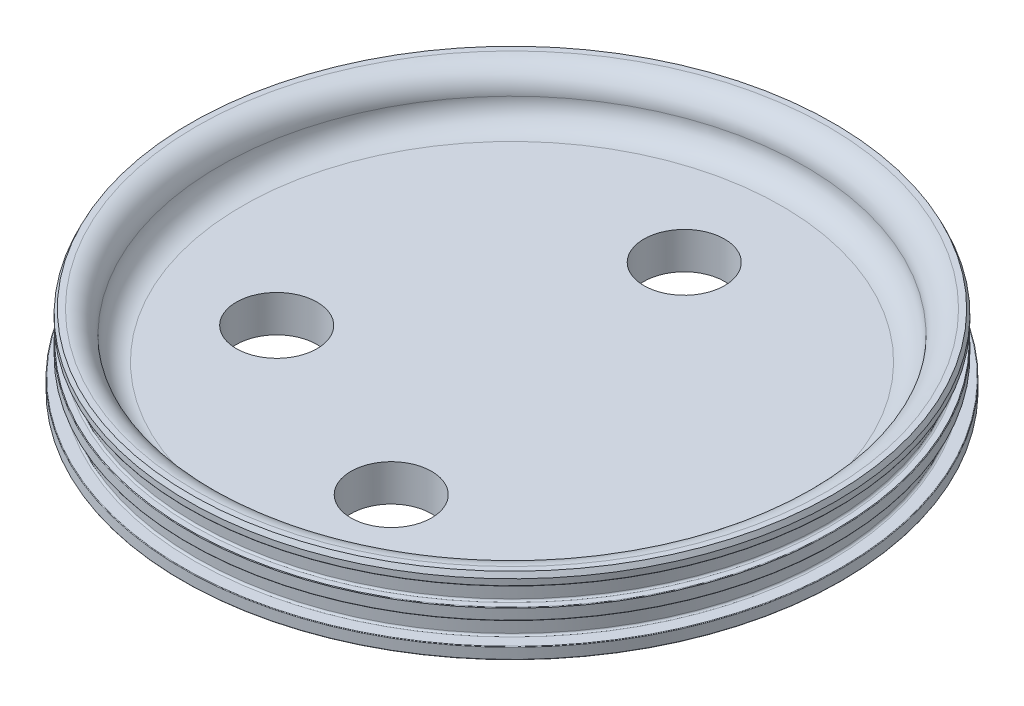
SolidWorks part; units mm, degrees
material "6061-T6 (SS)"
ref_plane "Front Plane" through (0, 0, 0) normal (0, 0, 1) x (1, 0, 0)
ref_plane "Top Plane" through (0, 0, 0) normal (0, 1, 0) x (1, 0, 0)
ref_plane "Right Plane" through (0, 0, 0) normal (1, 0, 0) x (0, 0, -1)
sketch "Sketch1" plane through (0, 0, 0) normal (0, 0, 1) x (1, 0, 0)
  line L0 (0, 48.1922) -> (0, -25.6743) construction
  line L1 (0, 0) -> (72.898, 0)
  line L2 (72.898, 0) -> (72.898, 2.54)
  line L3 (72.898, 2.54) -> (69.8475, 2.54)
  line L4 (69.8475, 2.54) -> (69.8475, 6.604)
  line L5 (69.8475, 6.604) -> (71.6255, 6.604)
  line L6 (71.6255, 6.604) -> (71.6255, 9.144)
  line L7 (71.6255, 9.144) -> (69.8475, 9.144)
  line L8 (64.7675, 15.748) -> (64.7675, 5.588)
  line L9 (64.7675, 5.588) -> (0, 5.588)
  line L10 (0, 5.588) -> (0, 0)
  line L11 (69.8475, 9.144) -> (69.8475, 13.208)
  line L12 (69.8475, 13.208) -> (71.6255, 13.208)
  line L13 (71.6255, 13.208) -> (71.6255, 15.748)
  line L14 (71.6255, 15.748) -> (64.7675, 15.748)
  dimension "D2" = 4.064
  dimension "D5" = 5.588
  dimension "D7" = 4.064
  dimension "D3" = 2.54
  dimension "D4" = 2.54
  dimension "D8" = 5.08
  dimension "D9" = 10.16
  dimension "D1" = 72.898
  dimension "D6" = 3.0505
  dimension "D10" = 1.778
revolve "Revolve1" add sketch "Sketch1" angle 360 about L0
sketch "Sketch6" plane through (0, 0, 0) normal (0, -1, 0) x (1, 0, 0)
  circle A0 centre (0, 0) radius 66.04
  dimension "D1" = 132.08
extrude "Boss-Extrude1" add sketch "Sketch6" along normal blind 2.54
fillet "CNC ID Fillet" radius 0.4064 5 edges at (-69.8475, 6.604, 0) (-69.8475, 2.54, 0) (66.04, 0, 0) (-69.8475, 13.208, 0) (-69.8475, 9.144, 0)
fillet "CNC OD Fillet" radius 0.127 6 edges at (-71.6255, 6.604, 0) (-72.898, 2.54, 0) (-71.6255, 9.144, 0) (-71.6255, 13.208, 0) (66.04, -2.54, 0) (-72.898, 0, 0)
chamfer "CNC Chamfers" distance 0.508 angle 65 1 edges at (-71.6255, 15.748, 0) first distance on face at (-64.7675, 15.748, 0)
hole_wizard "Pipe Tap Drill for 1/2 Tap - Fill Valve" positions "Sketch13" profile "Sketch14" hole size "1/2" standard "ANSI Inch" end condition through all
sketch "Sketch13" plane through (0, -2.54, 0) normal (0, -1, 0) x (-1, 0, 0)
  point P4 (0, 38.1)
  dimension "D1" = 38.1
sketch "Sketch14" plane through (0, -2.54, -38.1) normal (1, 0, 0) x (0, 0, -1)
  line L0 (0, 0) -> (0, 18.288)
  line L1 (0, 18.288) -> (8.9281, 18.288)
  line L2 (8.9281, 18.288) -> (8.9281, 0)
  line L5 (8.9281, 0) -> (0, 0)
  line L11 (0, -6.35) -> (0, 107.95) construction
  dimension "Thru Hole Dia." = 17.8562
  dimension "Thru Hole Depth" = 18.288
hole_wizard "Pipe Tap Drill for 1/4 Tap - Solenoid Valve" positions "Sketch15" profile "Sketch16" hole size "1/2" standard "ANSI Inch" end condition through all
sketch "Sketch15" plane through (0, -2.54, 0) normal (0, -1, 0) x (-1, 0, 0)
  line L2 (-12.0892, -38.8003) -> (0, 0) construction
  line L3 (0, 0) -> (0, -38.8003) construction
  point P4 (-12.0892, -38.8003)
  dimension "D1" = 17.306
  dimension "D2" = 40.64
  dimension "D3" = 38.8003
sketch "Sketch16" plane through (12.0892, -2.54, 38.8003) normal (1, 0, 0) x (0, 0, -1)
  line L0 (0, 0) -> (0, 18.288)
  line L1 (0, 18.288) -> (8.9281, 18.288)
  line L2 (8.9281, 18.288) -> (8.9281, 0)
  line L5 (8.9281, 0) -> (0, 0)
  line L11 (0, -6.35) -> (0, 107.95) construction
  dimension "Thru Hole Dia." = 17.8562
  dimension "Thru Hole Depth" = 18.288
hole_wizard "Pipe Tap Drill for 1/2 Tap - Cryo Valve" positions "Sketch17" profile "Sketch18" hole size "1/2" standard "ANSI Inch" end condition through all
sketch "Sketch17" plane through (0, -2.54, 0) normal (0, -1, 0) x (-1, 0, 0)
  line L0 (32.9956, -19.05) -> (17.2813, -19.05) construction
  line L2 (32.9956, -19.05) -> (0, 0) construction
  point P4 (32.9956, -19.05)
  dimension "D1" = 30
  dimension "D2" = 38.1
sketch "Sketch18" plane through (-32.9956, -2.54, 19.05) normal (1, 0, 0) x (0, 0, -1)
  line L0 (0, 0) -> (0, 18.288)
  line L1 (0, 18.288) -> (8.9281, 18.288)
  line L2 (8.9281, 18.288) -> (8.9281, 0)
  line L5 (8.9281, 0) -> (0, 0)
  line L11 (0, -6.35) -> (0, 107.95) construction
  dimension "Thru Hole Dia." = 17.8562
  dimension "Thru Hole Depth" = 18.288
fillet "Fillet1" radius 5.08 2 edges at (-64.7675, 5.588, 0) (-64.7675, 15.748, 0)
equation "\"D6@Sketch1\"=0.128-0.0079"
